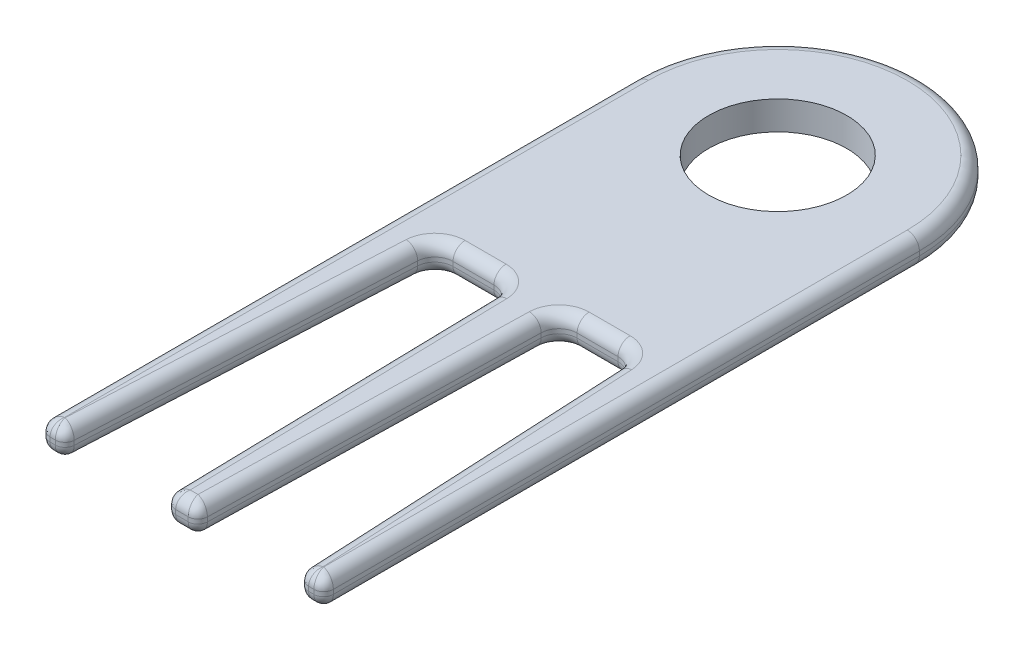
SolidWorks part; units mm, degrees
ref_plane "Front Plane" through (0, 0, 0) normal (0, 0, 1) x (1, 0, 0)
ref_plane "Top Plane" through (0, 0, 0) normal (0, 1, 0) x (1, 0, 0)
ref_plane "Right Plane" through (0, 0, 0) normal (1, 0, 0) x (0, 0, -1)
sketch "Sketch2" plane through (0, 0, 0) normal (1, 0, 0) x (0, 0, -1)
  line L2 (6.5, 3) -> (-6.5, 3) construction
  line L3 (6.5, 6.2) -> (-6.5, 6.2)
  dimension "D1" = 3.2
ref_plane "Plane1" through (0, 6.2, 0) normal (0, 1, 0) x (0, 0, 1)
sketch "Sketch3" plane through (0, 6.2, 0) normal (0, 1, 0) x (0, 0, 1)
  line L0 (-12, 0) -> (-5.3, 0)
  line L1 (49.2, 11.7) -> (49.2, 9.7)
  line L2 (49.2, 1.299) -> (49.2, 0)
  line L4 (20, 1.9661) -> (20, 8.24)
  line L5 (5.3, 0) -> (49.2, 0)
  line L11 (-12, 11.7) -> (49.2, 11.7)
  line L12 (-12, 11.7) -> (-12, 0)
  line L20 (20, 1.9661) -> (49.2, 1.299)
  line L21 (49.2, 9.7) -> (20, 8.24)
  arc A1 (5.3, 0) -> (-5.3, 0) centre (0, 0) ccw
  dimension "D1" = 11.7
  dimension "D2" = 20
extrude "Boss-Extrude1" add sketch "Sketch3" along normal blind 2.36
sketch "Sketch5" plane through (0, 6.2, 0) normal (0, 1, 0) x (0, 0, 1)
  line L0 (49.2, 11.7) -> (-12, 11.7) construction
  line L1 (0, 11.7) -> (0, 17.1392)
  line L2 (0, 17.1392) -> (-16.3974, 17.1392)
  line L3 (-16.3974, 17.1392) -> (-16.3974, -4.6342)
  line L4 (-16.3974, -4.6342) -> (-10.7431, -4.6342)
  arc A0 (0, 11.7) -> (-10.7431, -4.6342) centre (0, 0) ccw
  arc A1 (5.3, 0) -> (-5.3, 0) centre (0, 0) ccw construction
extrude "Cut-Extrude1" cut sketch "Sketch5" along normal blind 5
sketch "Sketch6" plane through (0, 6.2, 0) normal (0, 1, 0) x (0, 0, 1)
  circle A0 centre (0, 0) radius 5 construction
  arc A1 (5.3, 0) -> (-5.3, 0) centre (0, 0) ccw construction
  circle A2 centre (0, 0) radius 5.7
  dimension "D1" = 10
  dimension "D2" = 0.7
extrude "Cut-Extrude2" cut sketch "Sketch6" along normal blind 12
fillet "Fillet2" radius 1.5 2 edges at (1.9661, 7.38, 20) (8.24, 7.38, 20)
mirror "Mirror1" about plane through (0, 0, 0) normal (1, 0, 0) of bodies 104 101
fillet "Fillet3" radius 0.8 6 edges at (-11.7, 7.38, 49.2) (-9.7, 7.38, 49.2) (-1.299, 7.38, 49.2) (1.299, 7.38, 49.2) (9.7, 7.38, 49.2) (11.7, 7.38, 49.2)
fillet "Fillet4" radius 1 40 edges at (11.4657, 8.56, 48.9657) (10.6805, 8.56, 49.2) (9.9096, 8.56, 48.9796) (8.9866, 8.56, 34.9325) (7.847, 8.56, 20.4132) (5.1227, 8.56, 20) (2.3838, 8.56, 20.4273) (1.6248, 8.56, 34.942) (1.0763, 8.56, 48.9721) (0, 8.56, 49.2) (-1.0763, 8.56, 48.9721) (-1.6248, 8.56, 34.942) (-2.3838, 8.56, 20.4273) (-5.1227, 8.56, 20) (-7.847, 8.56, 20.4132) (-8.9866, 8.56, 34.9325) (-9.9096, 8.56, 48.9796) (-10.6805, 8.56, 49.2) (-11.4657, 8.56, 48.9657) (11.4657, 6.2, 48.9657) (10.6805, 6.2, 49.2) (9.9096, 6.2, 48.9796) (8.9866, 6.2, 34.9325) (7.847, 6.2, 20.4132) (5.1227, 6.2, 20) (2.3838, 6.2, 20.4273) (1.6248, 6.2, 34.942) (1.0763, 6.2, 48.9721) (0, 6.2, 49.2) (-1.0763, 6.2, 48.9721) (-1.6248, 6.2, 34.942) (-2.3838, 6.2, 20.4273) (-5.1227, 6.2, 20) (-7.847, 6.2, 20.4132) (-8.9866, 6.2, 34.9325) (-9.9096, 6.2, 48.9796) (-10.6805, 6.2, 49.2) (-11.4657, 6.2, 48.9657) (11.7, 8.56, 24.2) (11.7, 6.2, 24.2)
